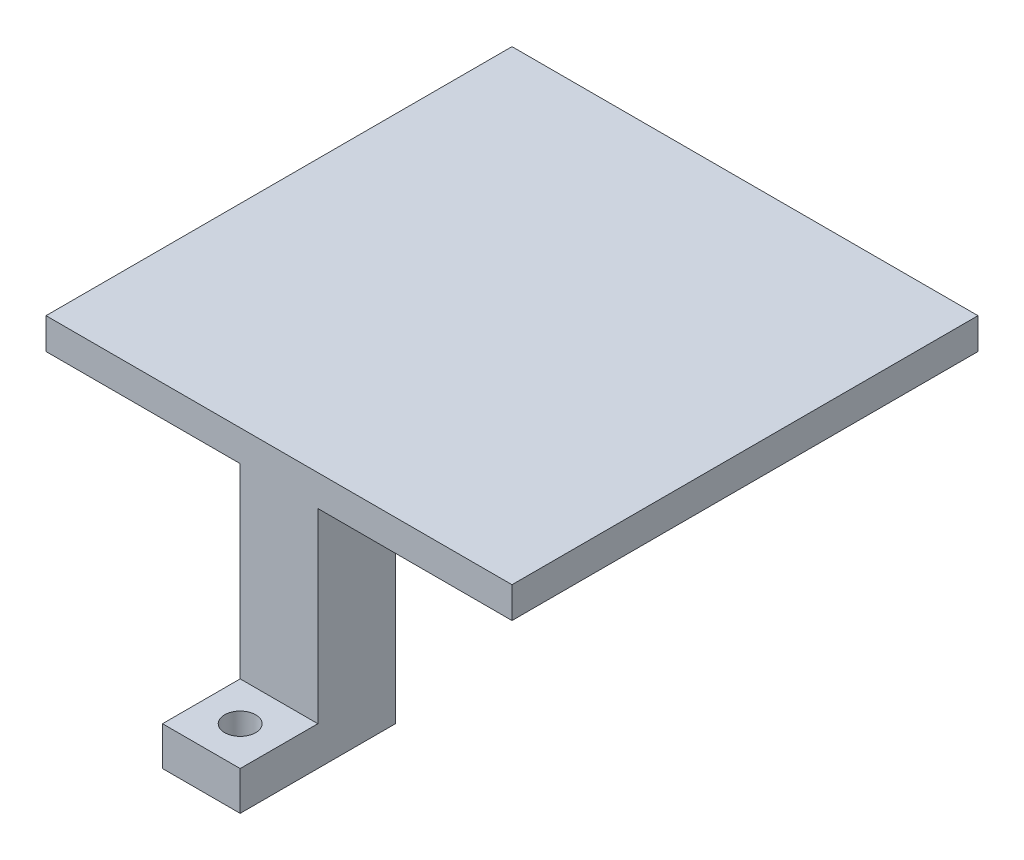
SolidWorks part; units mm, degrees
ref_plane "Front Plane" through (0, 0, 0) normal (0, 0, 1) x (1, 0, 0)
ref_plane "Top Plane" through (0, 0, 0) normal (0, 1, 0) x (1, 0, 0)
ref_plane "Right Plane" through (0, 0, 0) normal (1, 0, 0) x (0, 0, -1)
sketch "Sketch1" plane through (0, 0, 0) normal (0, 1, 0) x (1, 0, 0)
  line L1 (-15, 15) -> (15, 15)
  line L2 (-15, 15) -> (-15, -15)
  line L3 (-15, -15) -> (15, -15)
  line L4 (15, 15) -> (15, -15)
  line L5 (-15, 15) -> (15, -15) construction
  line L6 (-15, -15) -> (15, 15) construction
  point P0 (0, 0)
extrude "Boss-Extrude1" add sketch "Sketch1" along normal blind 2
sketch "Sketch2" plane through (0, 0, 0) normal (0, -1, 0) x (1, 0, 0)
  line L0 (0, 15) -> (-2.5, 15)
  line L1 (-15, 15) -> (15, 15) construction
  line L2 (-2.5, 15) -> (-2.5, 10)
  line L3 (-2.5, 10) -> (2.5, 10)
  line L4 (2.5, 10) -> (2.5, 15)
  line L5 (2.5, 15) -> (-2.5, 15)
  line M6 (15, 15) -> (-15, 15)
  dimension "D1" = 5
extrude "Boss-Extrude2" add sketch "Sketch2" along normal blind 14.5 contours L3 L4 L2 M6 region at (0, 0, 12.5)
sketch "Sketch3" plane through (0, 0, 15) normal (0, 0, 1) x (1, 0, 0)
  line L0 (-2.5, -14.5) -> (2.5, -14.5)
  line L1 (2.5, -14.5) -> (2.5, -12)
  line L2 (2.5, -14.5) -> (2.5, 0) construction
  line L3 (2.5, -12) -> (-2.5, -12)
  line L4 (-2.5, -14.5) -> (-2.5, 0) construction
  line L5 (-2.5, -12) -> (-2.5, -14.5)
extrude "Boss-Extrude3" add sketch "Sketch3" along normal blind 5
sketch "Sketch4" plane through (0, -14.5, 0) normal (0, -1, 0) x (-1, 0, 0)
  line L0 (-2.5, -10) -> (-2.5, -20) construction
  line L1 (2.5, -20) -> (-2.5, -20) construction
  circle A0 centre (0, -17.5) radius 1
  dimension "D1" = 2.5
  dimension "D2" = 2.5
extrude "Cut-Extrude1" cut sketch "Sketch4" against normal blind 5 contours A0
